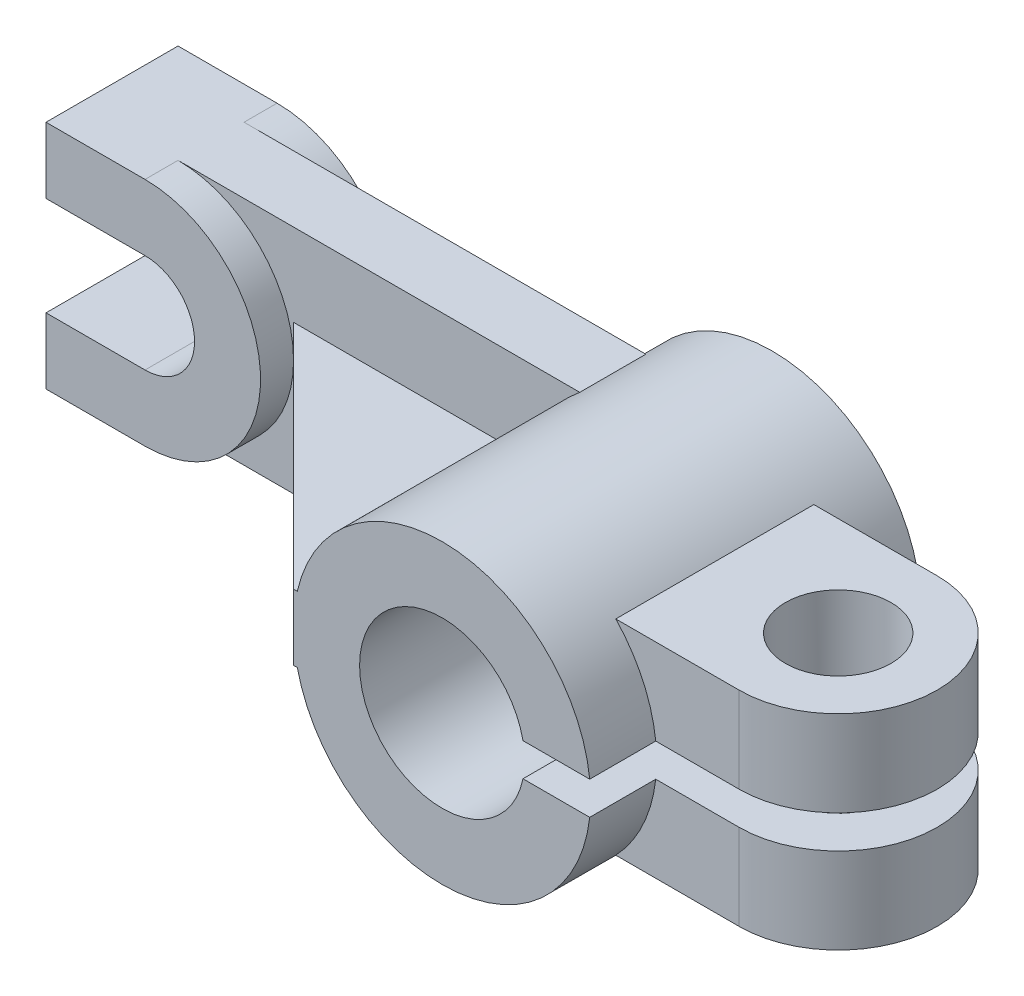
SolidWorks part; units mm, degrees
ref_plane "Front Plane" through (0, 0, 0) normal (0, 0, 1) x (1, 0, 0)
ref_plane "Top Plane" through (0, 0, 0) normal (0, 1, 0) x (1, 0, 0)
ref_plane "Right Plane" through (0, 0, 0) normal (1, 0, 0) x (0, 0, -1)
sketch "Sketch1" plane through (0, 0, 0) normal (0, 0, 1) x (1, 0, 0)
  line L0 (15, 0) -> (75.8579, 0)
  line L2 (75.8579, 35) -> (15, 35)
  arc A0 (15, 0) -> (15, 35) centre (15, 17.5) ccw
  arc A1 (75.8579, 35) -> (75.8579, 0) centre (90, 17.5) ccw
  dimension "D1" = 17.5
  dimension "D2" = 22.5
  dimension "D3" = 15
  dimension "D4" = 75.8579
extrude "Boss-Extrude1" add sketch "Sketch1" along normal blind 10
sketch "Sketch2" plane through (0, 0, 10) normal (0, 0, 1) x (1, 0, 0)
  line L2 (15, 10) -> (0, 10)
  line L3 (0, 10) -> (0, 0)
  line L4 (0, 0) -> (15, 0)
  line L5 (15, 25) -> (0, 25)
  line L6 (0, 25) -> (0, 35)
  line L7 (0, 35) -> (15, 35)
  line L8 (75.8579, 35) -> (15, 35) construction
  arc A0 (15, 0) -> (15, 35) centre (15, 17.5) ccw
  arc A1 (15, 10) -> (15, 25) centre (15, 17.5) ccw
  dimension "D1" = 7.5
extrude "Boss-Extrude2" add sketch "Sketch2" along normal blind 5 and the other way blind 15
sketch "Sketch3" plane through (0, 0, 10) normal (0, 0, 1) x (1, 0, 0)
  line L6 (102.2474, 20) -> (112.3607, 20)
  line L8 (102.2474, 15) -> (112.3607, 15)
  arc A0 (112.3607, 20) -> (112.3607, 15) centre (90, 17.5) ccw
  arc A3 (102.2474, 20) -> (102.2474, 15) centre (90, 17.5) ccw
  dimension "D1" = 22.5
  dimension "D2" = 12.5
  dimension "D3" = 26.3896
extrude "Boss-Extrude3" add sketch "Sketch3" along normal blind 35 and the other way blind 15
ref_plane "Plane1" through (0, 17.5, 0) normal (0, 1, 0) x (1, 0, 0)
sketch "Sketch19" plane through (0, 17.5, 0) normal (0, 1, 0) x (1, 0, 0)
  line L0 (32.5, -10) -> (67.5, -27.5)
  line L1 (67.5, -10) -> (67.5, -45) construction
rib "Rib27" sketch "Sketch19" sketch "Sketch19" thickness 10 extrusion direction parallel to sketch draft on no parameters "D1"=10
sketch "Sketch20" plane through (0, 17.5, 0) normal (0, 1, 0) x (1, 0, 0)
  line L0 (32.5, -10) -> (67.5, -45)
sketch "Sketch21" plane through (0, 0, 45) normal (0, 0, 1) x (1, 0, 0)
  line L2 (102.2474, 20) -> (112.3607, 20)
  line L3 (112.3607, 15) -> (102.2474, 15)
  arc A2 (102.2474, 20) -> (102.2474, 15) centre (90, 17.5) ccw
  arc A3 (112.3607, 20) -> (112.3607, 15) centre (90, 17.5) ccw
extrude "Boss-Extrude4" add sketch "Sketch21" along normal blind 5
rib "Rib29" sketch "Sketch20" sketch "Sketch20" thickness 10 extrusion direction parallel to sketch draft on no parameters "D1"=10
sketch "Sketch23" plane through (0, 0, 50) normal (0, 0, 1) x (1, 0, 0)
  line L2 (102.2474, 20) -> (112.3607, 20)
  line L3 (112.3607, 15) -> (102.2474, 15)
  arc A2 (102.2474, 20) -> (102.2474, 15) centre (90, 17.5) ccw
  arc A3 (112.3607, 20) -> (112.3607, 15) centre (90, 17.5) ccw
extrude "Cut-Extrude1" cut sketch "Sketch23" against normal blind 5
ref_plane "Plane4" through (67.5, 0, 0) normal (-1, 0, 0) x (0, 0, 1)
sketch "Sketch25" plane through (67.5, 0, 0) normal (-1, 0, 0) x (0, 0, 1)
  line L5 (45, 17.5) -> (45, 9.4497)
  line L6 (45, 9.4497) -> (52.5265, 9.4497)
  line L7 (52.5265, 9.4497) -> (52.5265, 28.6601)
  line L8 (52.5265, 28.6601) -> (45, 28.6601)
  line L9 (45, 28.6601) -> (45, 17.5)
  dimension "D1" = 52.5265
  dimension "D2" = 9.4497
  dimension "D3" = 28.6601
extrude "Cut-Extrude2" cut sketch "Sketch25" against normal blind 5
ref_plane "Plane9" through (0, 17.5, 0) normal (0, -1, 0) x (-1, 0, 0)
sketch "Sketch37" plane through (0, 17.5, 0) normal (0, -1, 0) x (-1, 0, 0)
  line L0 (-125, -5) -> (-112.5, -5)
  line L1 (-112.5, -35) -> (-125, -35)
  line L4 (-112.5, -5) -> (-112.5, -35)
  arc A2 (-125, -5) -> (-125, -35) centre (-125, -20) ccw
  circle A4 centre (-125, -20) radius 8
  dimension "D1" = 16
  dimension "D2" = 15
  dimension "D3" = 112.5
  dimension "D4" = 125
  dimension "D5" = 20
extrude "Boss-Extrude6" add sketch "Sketch37" along normal mid plane 31 separate body
sketch "Sketch45" plane through (112.5, 0, 0) normal (-1, 0, 0) x (0, 0, 1)
  line L1 (5, 2) -> (35, 2)
  line L4 (35, 2) -> (35, 17.5)
  line L5 (35, 2) -> (35, 33) construction
  line L6 (35, 17.5) -> (5, 17.5)
  line L7 (5, 2) -> (5, 33) construction
  line L8 (5, 17.5) -> (5, 2)
extrude "Boss-Extrude11" add sketch "Sketch45" along normal up to surface up to face at (80.9929, 17.5, 17.5)
sketch "Sketch48" plane through (112.5, 0, 0) normal (-1, 0, 0) x (0, 0, 1)
  line L0 (35, 33) -> (35, 17.5)
  line L1 (35, 17.5) -> (35, 33) construction
  line L2 (35, 17.5) -> (5, 17.5)
  line L3 (5, 17.5) -> (5, 33) construction
  line L4 (5, 17.5) -> (5, 33)
  line L5 (35, 33) -> (5, 33) construction
  line L6 (35, 33) -> (5, 33)
  line L7 (35, 17.5) -> (5, 17.5) construction
extrude "Boss-Extrude12" add sketch "Sketch48" along normal up to surface up to face at (88.2113, 15.1881, 18.125)
sketch "Sketch52" plane through (0, 0, 45) normal (0, 0, 1) x (1, 0, 0)
  line L0 (112.3607, 20) -> (146.0943, 20)
  line L1 (146.0943, 20) -> (146.0943, 15)
  line L2 (146.0943, 15) -> (112.3607, 15)
  line L3 (112.3607, 15) -> (112.3607, 20)
  line L4 (67.5, 22.5) -> (67.5, 12.5) construction
  dimension "D1" = 78.5943
extrude "Cut-Extrude4" cut sketch "Sketch52" against normal through all
